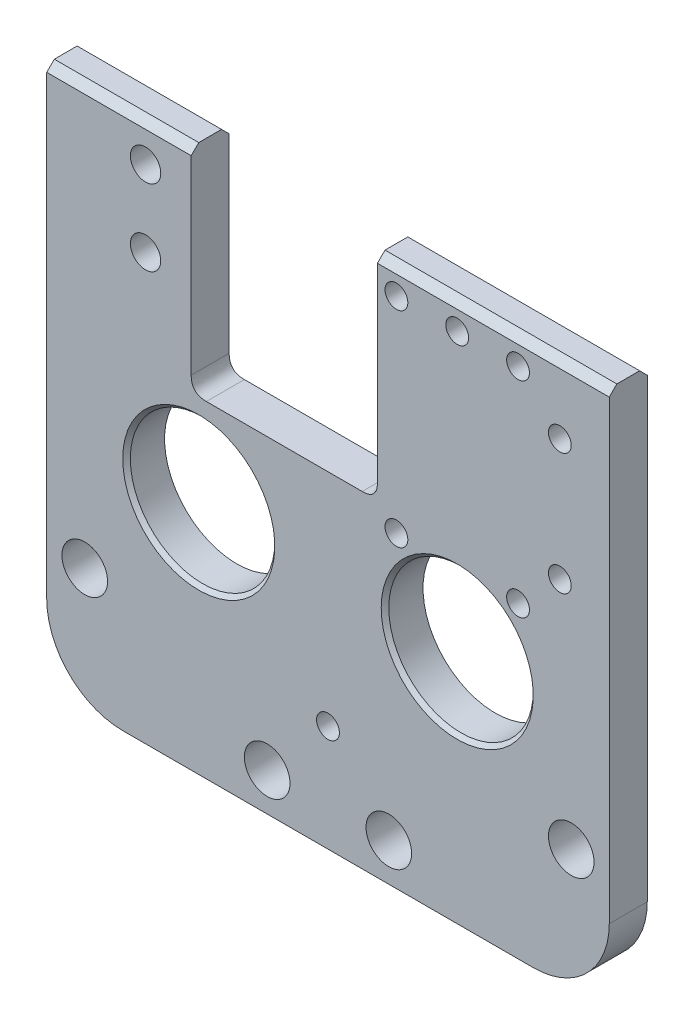
SolidWorks part; units mm, degrees
material "Stop 1060"
ref_plane "Płaszczyzna przednia" through (0, 0, 0) normal (0, 0, 1) x (1, 0, 0)
ref_plane "Płaszczyzna górna" through (0, 0, 0) normal (0, 1, 0) x (1, 0, 0)
ref_plane "Płaszczyzna prawa" through (0, 0, 0) normal (1, 0, 0) x (0, 0, -1)
sketch "Szkic1" plane through (0, 0, 0) normal (0, 0, 1) x (1, 0, 0)
  line L2 (34, 36) -> (34, -35)
  line L3 (34, -35) -> (-20, -35)
  line L6 (-20, -35) -> (-20, 36)
  line L7 (-20, 36) -> (34, 36)
  dimension "D1" = 71
  dimension "D2" = 20
  dimension "D3" = 54
  dimension "D4" = 36
extrude "Dodanie-wyciągnięcie1" add sketch "Szkic1" along normal blind 5
sketch "Szkic2" plane through (0, 0, 5) normal (0, 0, 1) x (1, 0, 0)
  line L1 (-20, 36) -> (3.5, 36)
  line L2 (-20, 36) -> (-20, 8)
  line L3 (-20, 8) -> (3.5, 8)
  line L4 (3.5, 36) -> (3.5, 8)
  dimension "D1" = 28
  dimension "D2" = 23.5
extrude "Wytnij-wyciągnięcie1" cut sketch "Szkic2" against normal blind 5
sketch "Szkic3" plane through (0, 0, 0) normal (0, 0, -1) x (-1, 0, 0)
  line L0 (-3.5, 8) -> (-3.5, 36) construction
  line L1 (-3.5, 30.5) -> (-24.5, 30.5)
  line L2 (-3.5, 30.5) -> (-3.5, 9.5)
  line L3 (-3.5, 9.5) -> (-24.5, 9.5)
  line L4 (-24.5, 30.5) -> (-24.5, 9.5)
  line L5 (-34, 36) -> (-3.5, 36) construction
  dimension "D1" = 5.5
  dimension "D2" = 21
  dimension "D3" = 21
extrude "Wytnij-wyciągnięcie2" cut sketch "Szkic3" against normal blind 3
sketch "Szkic4" plane through (0, 0, 5) normal (0, 0, 1) x (1, 0, 0)
  line L0 (3.5, 8) -> (3.5, 36) construction
  line L1 (34, 36) -> (3.5, 36) construction
  circle A0 centre (6, 32.5) radius 1.5
  circle A1 centre (14, 32.5) radius 1.5
  circle A2 centre (22, 32.5) radius 1.5
  circle A4 centre (22, 5.5) radius 1.5
  circle A5 centre (6, 5.5) radius 1.5
  circle A6 centre (27.5, 27) radius 1.5
  circle A7 centre (27.5, 11) radius 1.5
  circle A8 centre (14, 5.5) radius 1.5 [skipped]
  dimension "D1" = 2.5
  dimension "D2" = 3
  dimension "D4" = 3
  dimension "D6" = 8
  dimension "D8" = 5.5
  dimension "D10" = 3
  dimension "D3" = 3.5
  dimension "D5" = 2
  dimension "D7" = 27
  dimension "D9" = 5.5
  dimension "D11" = 2
extrude "Wytnij-wyciągnięcie3" cut sketch "Szkic4" against normal blind 5
sketch "Szkic5" plane through (0, 0, 5) normal (0, 0, 1) x (1, 0, 0)
  line L1 (-20, 8) -> (-40, 8)
  line L2 (-20, 8) -> (-20, -35)
  line L3 (-20, -35) -> (-40, -35)
  line L4 (-40, 8) -> (-40, -35)
  dimension "D1" = 20
  dimension "D2" = 43
extrude "Dodanie-wyciągnięcie2" add sketch "Szkic5" against normal blind 5
sketch "Szkic6" plane through (0, 0, 5) normal (0, 0, 1) x (1, 0, 0)
  line L0 (-40, 8) -> (-40, -35) construction
  line L1 (-40, 8) -> (3.5, 8) construction
  circle A0 centre (-20, -4) radius 9.5
  circle A1 centre (14, -4) radius 9.5
  dimension "D1" = 20
  dimension "D3" = 19
  dimension "D2" = 12
  dimension "D5" = 34
  dimension "D4" = 2
extrude "Wytnij-wyciągnięcie4" cut sketch "Szkic6" against normal blind 5
sketch "symetria" plane through (0, 0, 5) normal (0, 0, 1) x (1, 0, 0)
  line L0 (-20, -4) -> (14, -4)
  line L1 (-3, -4) -> (-3, -39)
  dimension "D1" = 35
sketch "Szkic7" plane through (0, 0, 5) normal (0, 0, 1) x (1, 0, 0)
  line L0 (-3, -4) -> (-3, -39) construction
  line L1 (-40, -35) -> (34, -35) construction
  line L2 (-3, -36.4153) -> (-3, -30)
  line L3 (-40, 8) -> (-40, -35) construction
  circle A0 centre (5, -30) radius 3
  circle A1 centre (-11, -30) radius 3
  circle A2 centre (-35, -19) radius 3
  circle A3 centre (29, -19) radius 3
  dimension "D1" = 6
  dimension "D4" = 6
  dimension "D2" = 8
  dimension "D3" = 5
  dimension "D5" = 5
  dimension "D6" = 16
extrude "Wytnij-wyciągnięcie5" cut sketch "Szkic7" against normal blind 10 contours A1 | A0 | A2 | A3 region at (5, -30, 5) region at (-11, -30, 5) region at (-35, -19, 5) region at (29, -19, 5)
fillet "Zaokrąglenie3" radius 10 2 edges at (34, -35, 2.5) (-40, -35, 2.5)
sketch "Szkic8" plane through (0, 0, 5) normal (0, 0, 1) x (1, 0, 0)
  line L1 (-40, 8) -> (-21, 8)
  line L2 (-40, 8) -> (-40, 36)
  line L3 (-40, 36) -> (-21, 36)
  line L4 (-21, 8) -> (-21, 36)
  dimension "D1" = 19
  dimension "D2" = 28
extrude "Dodanie-wyciągnięcie3" add sketch "Szkic8" against normal blind 5
fillet "Zaokrąglenie2" radius 2 2 edges at (3.5, 8, 2.5) (-21, 8, 2.5) conic rho 0.5
sketch "Szkic9" plane through (0, 0, 5) normal (0, 0, 1) x (1, 0, 0)
  line L2 (-21, 10) -> (-21, 36) construction
  line L3 (-21, 36) -> (-40, 36) construction
  circle A1 centre (-27, 31) radius 2
  circle A2 centre (-27, 21) radius 2
  dimension "D1" = 6
  dimension "D2" = 6
  dimension "D3" = 4
  dimension "D4" = 4
  dimension "D6" = 10
  dimension "D5" = 5
extrude "Wytnij-wyciągnięcie6" cut sketch "Szkic9" against normal blind 10
chamfer "Sfazowanie2" distance 1 angle 45 4 edges at (18.75, 36, 5) (18.75, 36, 0) (-30.5, 36, 0) (-30.5, 36, 5)
chamfer "Sfazowanie3" distance 0.5 angle 45 2 edges at (-10.5, -4, 5) (23.5, -4, 5)
sketch "Szkic10" plane through (0, 0, 5) normal (0, 0, 1) x (1, 0, 0)
  line L0 (-3, -4) -> (-3, -39) construction
  line L1 (-30, -35) -> (24, -35) construction
  circle A0 centre (-3, -21) radius 1.5
  dimension "D1" = 14
  dimension "D2" = 3
extrude "Wytnij-wyciągnięcie7" cut sketch "Szkic10" against normal blind 10
